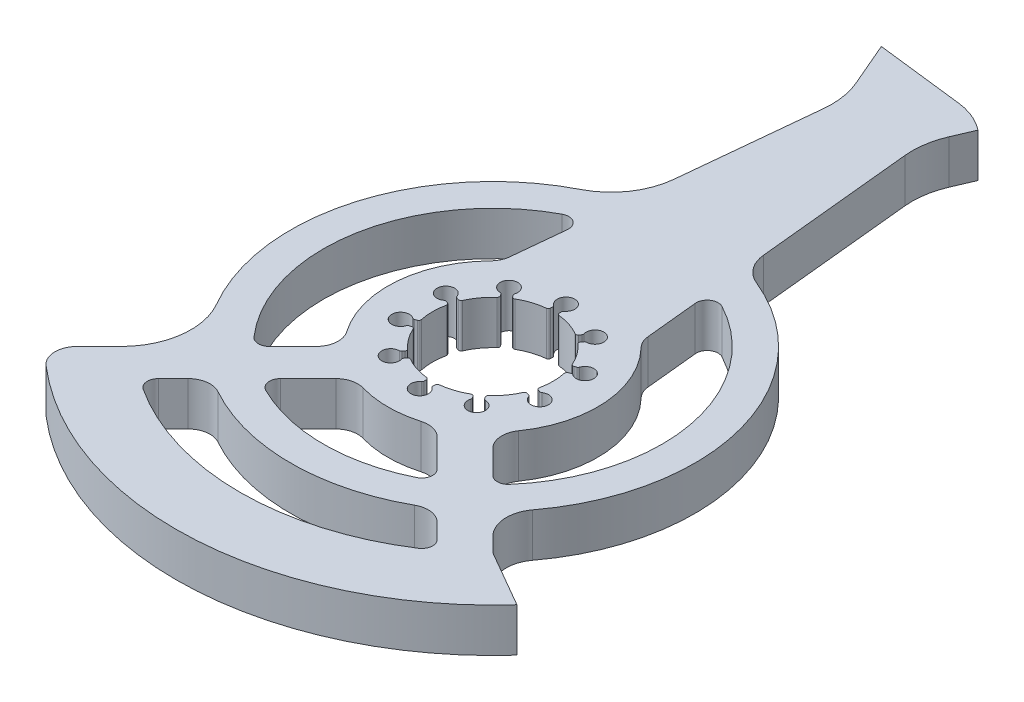
SolidWorks part; units mm, degrees
material "AISI Type A2 Tool Steel"
ref_plane "Front Plane" through (0, 0, 0) normal (0, 0, 1) x (1, 0, 0)
ref_plane "Top Plane" through (0, 0, 0) normal (0, 1, 0) x (1, 0, 0)
ref_plane "Right Plane" through (0, 0, 0) normal (1, 0, 0) x (0, 0, -1)
other "Center of Mass"
other "Bounding Box"
ref_plane "Default Plane" through (0, 2.286, 19.05) normal (0, -1, 0) x (-1, 0, 0)
sketch "Sketch1" plane through (0, 0, 0) normal (0, 1, 0) x (1, 0, 0)
  circle A0 centre (0, 0) radius 133.35 construction
  circle A1 centre (0, 0) radius 30.48
  circle A2 centre (0, 0) radius 17.4625
  dimension "D1" = 266.7
  dimension "D2" = 60.96
  dimension "D3" = 34.925
extrude "Boss-Extrude1" add sketch "Sketch1" along normal mid plane 12.7
sketch "Sketch2" plane through (0, 6.35, 0) normal (0, 1, 0) x (1, 0, 0)
  line L0 (-11.811, 107.95) -> (-20.32, 22.7185)
  line L1 (20.32, 22.7185) -> (11.811, 107.95)
  line L4 (0, 0) -> (0, 133.35) construction
  line L5 (-11.811, 107.95) -> (0, 107.95) construction
  line L6 (0, 107.95) -> (11.811, 107.95) construction
  line L7 (-19.05, 131.9823) -> (0, 0) construction
  line L8 (-19.05, 131.9823) -> (82.4889, -104.775) construction
  line L9 (-19.05, 131.9823) -> (-13.5301, 119.1117)
  line L10 (19.05, 131.9823) -> (13.5301, 119.1117)
  circle A0 centre (0, 0) radius 133.35 construction
  circle A1 centre (0, 0) radius 133.35 construction
  arc A2 (-19.05, 131.9823) -> (19.05, 131.9823) centre (0, 0) cw
  circle A5 centre (0, 0) radius 30.48
  arc A6 (20.32, 22.7185) -> (-20.32, 22.7185) centre (0, 0) ccw
  arc A7 (-20.32, 22.7185) -> (20.32, 22.7185) centre (0, 0) ccw construction
  arc A9 (-13.5301, 119.1117) -> (-11.811, 107.95) centre (-34.3168, 110.1968) cw
  arc A10 (13.5301, 119.1117) -> (11.811, 107.95) centre (34.3168, 110.1968) ccw
  dimension "D3" = 38.1
  dimension "D4" = 25.4
  dimension "D5" = 40.64
  dimension "D6" = 11.811
  dimension "D1" = 15
  dimension "D2" = 0
extrude "Boss-Extrude2" add sketch "Sketch2" against normal through all
sketch "Sketch3" plane through (0, 6.35, 0) normal (0, 1, 0) x (1, 0, 0)
  line L0 (-65.1069, -65.1069) -> (-21.5526, -21.5526)
  line L1 (21.5526, -21.5526) -> (65.1069, -65.1069)
  line L2 (0, -30.48) -> (0, -92.075) construction
  line L4 (-21.5526, -21.5526) -> (0, 0) construction
  line L5 (0, 0) -> (21.5526, -21.5526) construction
  arc A0 (-65.1069, -65.1069) -> (65.1069, -65.1069) centre (0, 0) ccw
  circle A1 centre (0, 0) radius 30.48 construction
  arc A3 (-21.5526, -21.5526) -> (21.5526, -21.5526) centre (0, 0) ccw
  point P13 (0, -92.075)
  dimension "D2" = 92.075
  dimension "D1" = 90
extrude "Boss-Extrude3" add sketch "Sketch3" against normal through all
sketch "Sketch5" plane through (0, 6.35, 0) normal (0, 1, 0) x (1, 0, 0)
  line L0 (0, 17.4625) -> (0, 21.2725) construction
  line L2 (-1.27, 17.4163) -> (1.27, 17.4163)
  line L3 (-1.27, 17.4163) -> (-1.27, 19.0581)
  line L5 (1.27, 17.4163) -> (1.27, 19.0581)
  arc A0 (1.27, 19.0581) -> (-1.27, 19.0581) centre (0, 21.2725) ccw
  circle A1 centre (0, 0) radius 17.4625 construction
  circle A2 centre (0, 21.2725) radius 4.5847 construction
  arc A3 (1.27, 19.0581) -> (-1.27, 19.0581) centre (0, 21.2725) cw construction
  point P10 (0, 18.7198)
  dimension "D2" = 5.1054
  dimension "D4" = 9.1694
  dimension "D1" = 3.81
  dimension "D3" = 2.54
extrude "Cut-Extrude2" cut sketch "Sketch5" against normal through all
pattern_circular "CirPattern1" count 10 over 360 about axis through (0, 6.35, 0) along (0, -1, 0) of "Cut-Extrude2"
sketch "Sketch6" plane through (0, 6.35, 0) normal (0, 1, 0) x (1, 0, 0)
  circle A0 centre (0, 0) radius 17.526
  arc A1 (-11.2645, 13.3436) -> (-16.1714, 6.5898) centre (0, 0) ccw construction
  dimension "D1" = 0.0635
extrude "Cut-Extrude3" cut sketch "Sketch6" against normal through all
sketch "Sketch7" plane through (0, 6.35, 0) normal (0, 1, 0) x (1, 0, 0)
  line L0 (-43.2269, -59.3914) -> (-11.8976, -28.062)
  line L1 (11.8976, -28.062) -> (43.2269, -59.3914)
  line L3 (-21.5526, -21.5526) -> (-65.1069, -65.1069) construction
  line L4 (65.1069, -65.1069) -> (21.5526, -21.5526) construction
  line L5 (-43.2269, -59.3914) -> (-51.3091, -51.3091) construction
  line L6 (43.2269, -59.3914) -> (51.3091, -51.3091) construction
  arc A0 (-11.8976, -28.062) -> (11.8976, -28.062) centre (0, 0) ccw
  arc A1 (-43.2269, -59.3914) -> (43.2269, -59.3914) centre (0, 0) ccw
  arc A2 (-65.1069, -65.1069) -> (65.1069, -65.1069) centre (0, 0) ccw construction
  arc A4 (21.5526, -21.5526) -> (20.32, 22.7185) centre (0, 0) ccw construction
  dimension "D1" = 18.6182
  dimension "D2" = 11.43
extrude "Cut-Extrude4" cut sketch "Sketch7" against normal through all
sketch "Sketch8" plane through (0, 6.35, 0) normal (0, 1, 0) x (1, 0, 0)
  circle A0 centre (0, 0) radius 49.2125
  circle A1 centre (0, 0) radius 58.7375
  dimension "D1" = 9.525
  dimension "D2" = 117.475
extrude "Boss-Extrude4" add sketch "Sketch8" against normal through all
sketch "Sketch11" plane through (0, 6.35, 0) normal (0, 1, 0) x (1, 0, 0)
  line L0 (-8.1697, 29.3647) -> (-6.2277, 48.8169)
  line L1 (6.2277, 48.8169) -> (8.1697, 29.3647)
  line L3 (-18.0161, 45.7962) -> (-20.32, 22.7185) construction
  line L4 (20.32, 22.7185) -> (18.0161, 45.7962) construction
  line L5 (-7.1987, 39.0908) -> (-18.5721, 40.2263) construction
  line L6 (7.1987, 39.0908) -> (18.5721, 40.2263) construction
  arc A0 (-8.1697, 29.3647) -> (8.1697, 29.3647) centre (0, 0) cw
  arc A1 (-6.2277, 48.8169) -> (6.2277, 48.8169) centre (0, 0) cw
  arc A2 (-20.32, 22.7185) -> (-21.5526, -21.5526) centre (0, 0) ccw construction
  arc A3 (-18.0161, 45.7962) -> (-34.7985, -34.7985) centre (0, 0) ccw construction
  dimension "D1" = 11.43
extrude "Cut-Extrude6" [suppressed] cut sketch "Sketch11" against normal through all
sketch "Sketch13" plane through (0, 6.35, 0) normal (0, 1, 0) x (1, 0, 0)
  line L0 (13.5301, 119.1117) -> (19.05, 131.9823) construction
  line L1 (16.0465, 124.9792) -> (19.05, 131.9823)
  line L2 (-19.05, 131.9823) -> (6.4955, 128.9421)
  line L3 (-18.4986, 132.0619) -> (49468.6673, 7274.919) construction
  arc A2 (19.05, 131.9823) -> (-19.05, 131.9823) centre (0, 0) ccw construction
  arc A4 (19.05, 131.9823) -> (-19.05, 131.9823) centre (0, 0) ccw
  arc A5 (6.4955, 128.9421) -> (16.0465, 124.9792) centre (4.2442, 110.0256) cw
  dimension "D1" = 19.05
  dimension "D2" = 7.62
  dimension "D3" = 15
extrude "Cut-Extrude7" cut sketch "Sketch13" against normal through all
sketch "Sketch15" plane through (0, 6.35, 0) normal (0, 1, 0) x (1, 0, 0)
  line L0 (68.5149, -61.5103) -> (51.9418, -51.9418)
  line L1 (65.1069, -65.1069) -> (41.5337, -41.5337) construction
  line L2 (51.9418, -51.9418) -> (65.1069, -65.1069)
  arc A0 (65.1069, -65.1069) -> (68.5149, -61.5103) centre (0, 0) ccw
  arc A1 (-43.2269, -59.3914) -> (43.2269, -59.3914) centre (0, 0) ccw construction
  point P5 (70.8, -58.8656)
  point P9 (56.8688, -56.8688)
  dimension "D1" = 15
extrude "Boss-Extrude5" add sketch "Sketch15" against normal up to surface (12.7 mm away) up to face at (0.2897, -6.35, -55.9264)
fillet "Fillet1" radius 6.35 8 edges at (-21.5526, 0, 21.5526) (21.5526, 0, 21.5526) (20.32, 0, -22.7185) (-20.32, 0, -22.7185) (11.8976, 0, 28.062) (-11.8976, 0, 28.062) (32.6575, 0, 48.8219) (-32.6575, 0, 48.8219)
fillet "Fillet6" radius 0.635 20 edges at (-11.3019, 0, -13.3951) (-16.2319, 0, -6.6094) (-17.0168, 0, -4.1938) (-17.0168, 0, 4.1938) (-16.2319, 0, 6.6094) (-11.3019, 0, 13.3951) (-9.247, 0, 14.888) (-1.27, 0, 17.4799) (1.27, 0, 17.4799) (9.247, 0, 14.888) (11.3019, 0, 13.3951) (16.2319, 0, 6.6094) (17.0168, 0, 4.1938) (17.0168, 0, -4.1938) (16.2319, 0, -6.6094) (11.3019, 0, -13.3951) (9.247, 0, -14.888) (1.27, 0, -17.4799) (-1.27, 0, -17.4799) (-9.247, 0, -14.888)
fillet "Fillet7" radius 3.175 8 edges at (-25.7647, 0, 41.9291) (25.7647, 0, 41.9291) (34.7985, 0, 34.7985) (-34.7985, 0, 34.7985) (-18.0161, 0, -45.7962) (18.0161, 0, -45.7962) (43.2269, 0, 59.3914) (-43.2269, 0, 59.3914)
fillet "Fillet8" radius 9.525 2 edges at (16.9743, 0, -56.2314) (41.5337, 0, 41.5337)
fillet "Fillet9" [suppressed] radius 3.175
fillet "Fillet10" radius 0.635 20 edges at (-12.2295, 0, -14.6719) (-10.1746, 0, -16.1648) (-18.5178, 0, -4.6814) (-17.7329, 0, -7.0971) (-18.5178, 0, 4.6814) (-17.7329, 0, 7.0971) (-10.1746, 0, 16.1648) (-12.2295, 0, 14.6719) (-1.27, 0, 19.0581) (1.27, 0, 19.0581) (12.2295, 0, 14.6719) (10.1746, 0, 16.1648) (17.7329, 0, 7.0971) (18.5178, 0, 4.6814) (18.5178, 0, -4.6814) (17.7329, 0, -7.0971) (12.2295, 0, -14.6719) (10.1746, 0, -16.1648) (-1.27, 0, -19.0581) (1.27, 0, -19.0581)
fillet "Fillet11" radius 6.35 1 edges at (-65.1069, 0, 65.1069)
fillet "Fillet12" radius 20.32 2 edges at (-41.5337, 0, 41.5337) (-16.9743, 0, -56.2314)
equation "\"Unit Measure\"= \"BoundingVolume\" / \"Thickness\"'in^2"
